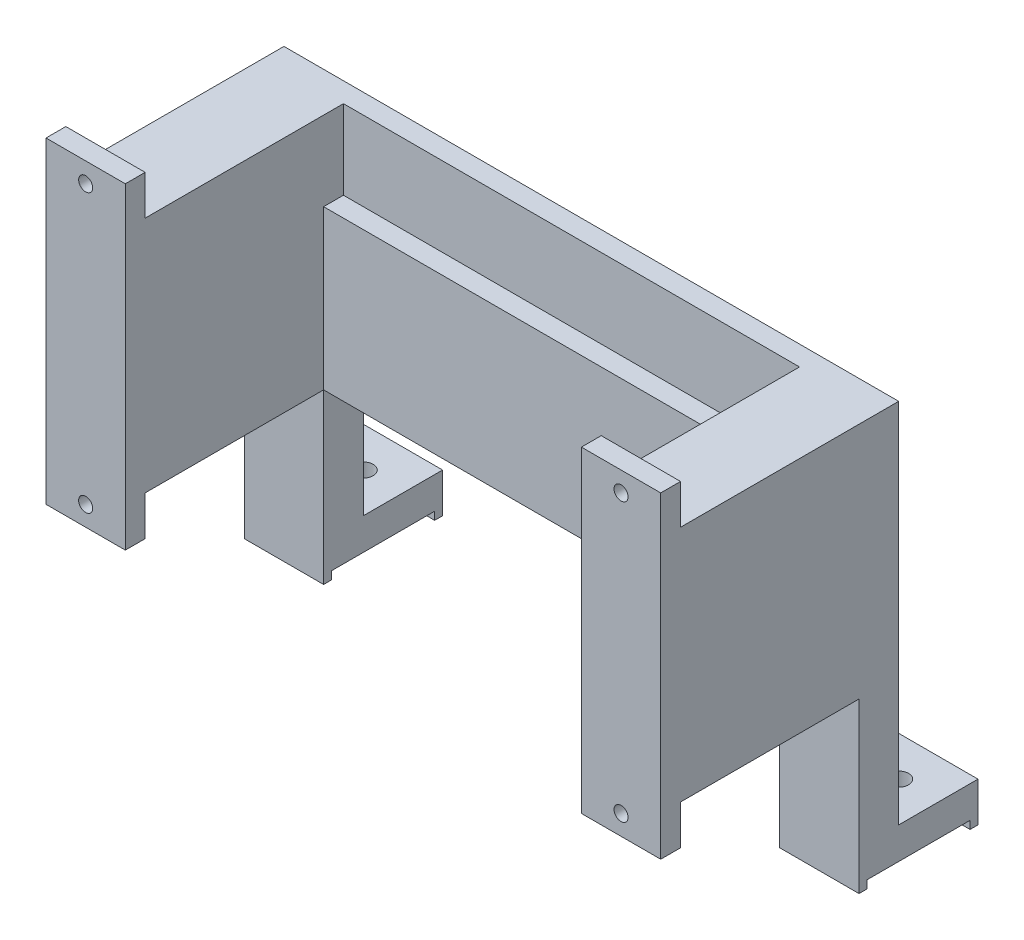
SolidWorks part; units mm, degrees
material "6061 Alloy"
ref_plane "Front Plane" through (0, 0, 0) normal (0, 0, 1) x (1, 0, 0)
ref_plane "Top Plane" through (0, 0, 0) normal (0, 1, 0) x (1, 0, 0)
ref_plane "Right Plane" through (0, 0, 0) normal (1, 0, 0) x (0, 0, -1)
sketch "Sketch1" plane through (0, 0, 0) normal (0, 1, 0) x (1, 0, 0)
  line L1 (-98.425, -38.1) -> (98.425, -38.1)
  line L2 (-98.425, -38.1) -> (-98.425, 38.1)
  line L3 (-98.425, 38.1) -> (98.425, 38.1)
  line L4 (98.425, -38.1) -> (98.425, 38.1)
  line L5 (-98.425, -38.1) -> (98.425, 38.1) construction
  line L6 (-98.425, 38.1) -> (98.425, -38.1) construction
  point P0 (0, 0)
  dimension "D1" = 76.2
  dimension "D2" = 196.85
extrude "Boss-Extrude1" add sketch "Sketch1" along normal blind 76.2
sketch "Sketch3" plane through (0, 76.2, 0) normal (0, 1, 0) x (1, 0, 0)
  line L0 (-98.425, -38.1) -> (98.425, -38.1) construction
  line L1 (-73.025, -38.1) -> (73.025, -38.1)
  line L2 (-73.025, -38.1) -> (-73.025, 25.4)
  line L3 (-73.025, 25.4) -> (73.025, 25.4)
  line L4 (73.025, -38.1) -> (73.025, 25.4)
  line L5 (-98.425, 38.1) -> (-98.425, -38.1) construction
  line L6 (98.425, -38.1) -> (98.425, 38.1) construction
  dimension "D1" = 63.5
  dimension "D2" = 25.4
  dimension "D3" = 25.4
extrude "Cut-Extrude1" cut sketch "Sketch3" against normal through all
sketch "Sketch9" plane through (0, 76.2, 0) normal (0, 1, 0) x (1, 0, 0)
  line L0 (73.025, 25.4) -> (-73.025, 25.4) construction
  line L1 (-73.025, 31.75) -> (73.025, 31.75)
  line L2 (-73.025, 31.75) -> (-73.025, 17.2824)
  line L3 (-73.025, 17.2824) -> (73.025, 17.2824)
  line L4 (73.025, 31.75) -> (73.025, 17.2824)
  line L5 (-73.025, 31.75) -> (73.025, 17.2824) construction
  line L6 (-73.025, 17.2824) -> (73.025, 31.75) construction
  point P0 (0, 24.5162)
  dimension "D1" = 6.35
  dimension "D2" = 146.05
  dimension "D3" = 73.025
extrude "Cut-Extrude3" cut sketch "Sketch9" against normal blind 25.4
sketch "Sketch4" plane through (0, 0, -38.1) normal (0, 0, -1) x (-1, 0, 0)
  line L1 (-98.425, 0) -> (-73.025, 0)
  line L2 (-98.425, 0) -> (-98.425, -53.975)
  line L3 (-98.425, -53.975) -> (-73.025, -53.975)
  line L4 (-73.025, 0) -> (-73.025, -53.975)
  dimension "D1" = 53.975
  dimension "D2" = 25.4
extrude "Boss-Extrude2" add sketch "Sketch4" against normal blind 12.7
sketch "Sketch5" plane through (0, 0, -38.1) normal (0, 0, -1) x (-1, 0, 0)
  line L0 (-73.025, -53.975) -> (-73.025, 0) construction
  line L1 (-98.425, -53.975) -> (-73.025, -53.975)
  line L2 (-98.425, -53.975) -> (-98.425, -41.275)
  line L3 (-98.425, -41.275) -> (-73.025, -41.275)
  line L4 (-73.025, -53.975) -> (-73.025, -41.275)
  dimension "D1" = 12.7
extrude "Boss-Extrude3" add sketch "Sketch5" along normal blind 25.4
sketch "Sketch6" plane through (98.425, 0, 0) normal (1, 0, 0) x (0, 0, -1)
  line L0 (25.4, -53.975) -> (63.5, -53.975) construction
  line L1 (27.94, -53.975) -> (60.96, -53.975)
  line L2 (27.94, -53.975) -> (27.94, -51.435)
  line L3 (27.94, -51.435) -> (60.96, -51.435)
  line L4 (60.96, -53.975) -> (60.96, -51.435)
  line L5 (25.4, 0) -> (25.4, -53.975) construction
  line L6 (63.5, -41.275) -> (63.5, -53.975) construction
  dimension "D1" = 2.54
  dimension "D2" = 2.54
  dimension "D3" = 2.54
extrude "Cut-Extrude2" cut sketch "Sketch6" against normal through all
hole_wizard "1/4 (0.25) Diameter Hole1" positions "Sketch7" profile "Sketch8" hole size "1/4" standard "ANSI Inch" end condition through all
sketch "Sketch7" plane through (0, -41.275, 0) normal (0, 1, 0) x (1, 0, 0)
  line L0 (73.025, 63.5) -> (98.425, 63.5) construction
  line L1 (98.425, 63.5) -> (98.425, 38.1) construction
  point P0 (85.725, 50.8)
  dimension "D1" = 12.7
  dimension "D2" = 12.7
sketch "Sketch8" plane through (85.725, -41.275, -50.8) normal (1, 0, 0) x (0, 0, 1)
  line L0 (0, 0) -> (0, 12.7)
  line L1 (0, 12.7) -> (3.175, 12.7)
  line L2 (3.175, 12.7) -> (3.175, 0)
  line L5 (3.175, 0) -> (0, 0)
  line L11 (0, -6.35) -> (0, 107.95) construction
  dimension "Thru Hole Dia." = 6.35
  dimension "Thru Hole Depth" = 12.7
sketch "Sketch11" plane through (0, 0, 38.1) normal (0, 0, 1) x (1, 0, 0)
  line L0 (98.425, 0) -> (98.425, -53.975) construction
  line L1 (73.025, 76.2) -> (98.425, 76.2)
  line L2 (73.025, 76.2) -> (73.025, 88.9)
  line L3 (73.025, 88.9) -> (98.425, 88.9)
  line L4 (98.425, 76.2) -> (98.425, 88.9)
  line L5 (73.025, 0) -> (98.425, 0)
  line L6 (73.025, 0) -> (73.025, -12.7)
  line L7 (73.025, -12.7) -> (98.425, -12.7)
  line L8 (98.425, 0) -> (98.425, -12.7)
  dimension "D1" = 25.4
  dimension "D2" = 12.7
  dimension "D3" = 12.7
extrude "Boss-Extrude4" add sketch "Sketch11" against normal blind 6.35
hole_wizard "#8 Clearance Hole1" positions "Sketch12" profile "Sketch13" hole size "#8" standard "ANSI Inch" end condition up to next
sketch "Sketch12" plane through (0, 0, 38.1) normal (0, 0, 1) x (1, 0, 0)
  line L0 (98.425, 88.9) -> (73.025, 88.9) construction
  line L1 (73.025, -12.7) -> (73.025, 88.9) construction
  line L2 (73.025, -12.7) -> (98.425, -12.7) construction
  point P0 (85.725, 82.55)
  point P2 (85.725, -6.35)
  dimension "D1" = 6.35
  dimension "D2" = 12.7
  dimension "D3" = 12.7
  dimension "D4" = 6.35
sketch "Sketch13" plane through (85.725, 82.55, 38.1) normal (1, 0, 0) x (0, -1, 0)
  line L0 (0, 0) -> (0, 6.35)
  line L1 (0, 6.35) -> (2.2479, 6.35)
  line L2 (2.2479, 6.35) -> (2.2479, 0)
  line L5 (2.2479, 0) -> (0, 0)
  line L11 (0, -6.35) -> (0, 107.95) construction
  dimension "Thru Hole Dia." = 4.4958
  dimension "Thru Hole Depth" = 6.35
mirror "Mirror1" about plane through (0, 0, 0) normal (1, 0, 0) of "#8 Clearance Hole1", "Boss-Extrude4", "Boss-Extrude2", "1/4 (0.25) Diameter Hole1", "Cut-Extrude2", "Boss-Extrude3"
